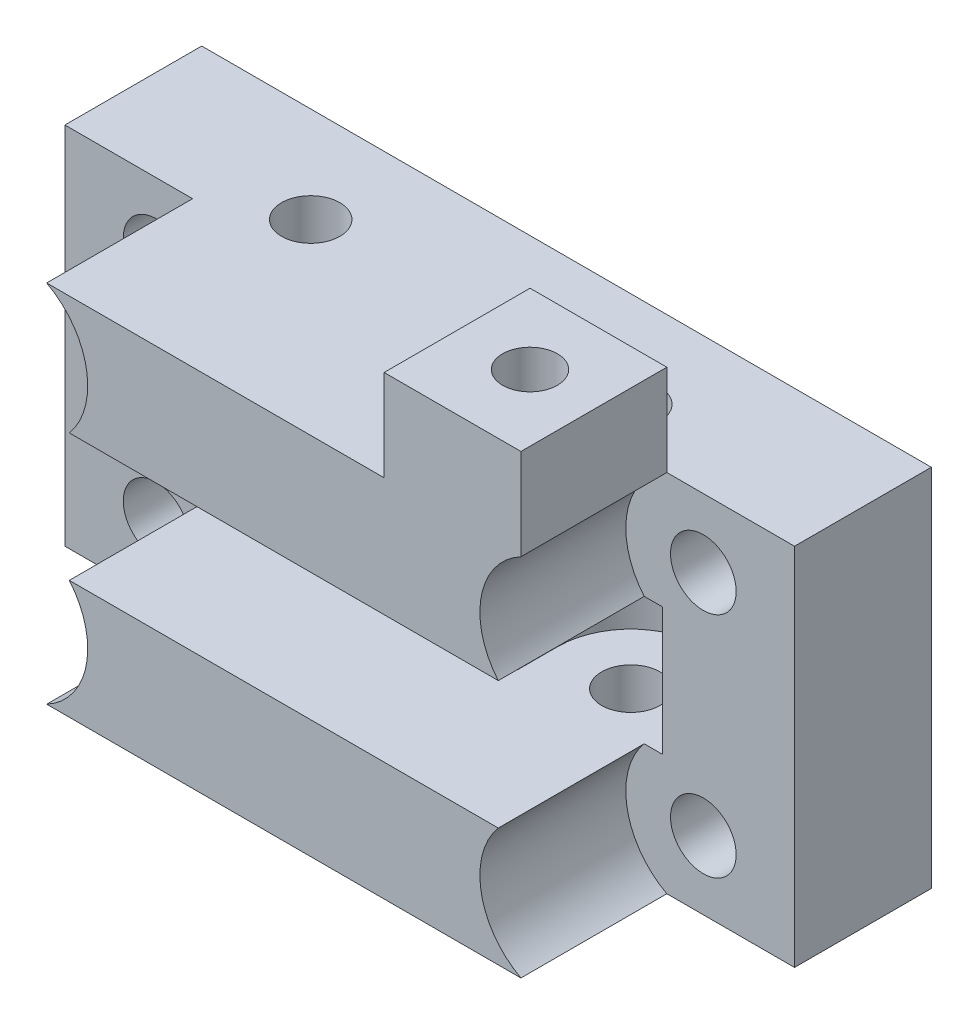
SolidWorks part; units mm, degrees
ref_plane "Front Plane" through (0, 0, 0) normal (0, 0, 1) x (1, 0, 0)
ref_plane "Top Plane" through (0, 0, 0) normal (0, 1, 0) x (1, 0, 0)
ref_plane "Right Plane" through (0, 0, 0) normal (1, 0, 0) x (0, 0, -1)
sketch "Sketch1" plane through (0, 0, 0) normal (0, 0, 1) x (1, 0, 0)
  line L0 (-25.4, 12.7) -> (25.4, -12.7) construction
  line L1 (-25.4, -12.7) -> (25.4, -12.7)
  line L2 (-25.4, -12.7) -> (-25.4, 12.7)
  line L3 (-25.4, 12.7) -> (25.4, 12.7)
  line L4 (25.4, -12.7) -> (25.4, 12.7)
  point P6 (0, 0)
  dimension "D1" = 50.8
  dimension "D2" = 25.4
extrude "Boss-Extrude1" add sketch "Sketch1" along normal mid plane 9.525
sketch "Sketch2" plane through (0, 0, 4.7625) normal (0, 0, 1) x (1, 0, 0)
  line L0 (-25.4, -12.7) -> (25.4, -12.7) construction
  line L1 (-25.4, 12.7) -> (-25.4, -12.7) construction
  circle A0 centre (-19.05, 7.9375) radius 2.286
  dimension "D1" = 4.572
  dimension "D2" = 20.6375
  dimension "D3" = 6.35
extrude "Cut-Extrude1" cut sketch "Sketch2" against normal through all
sketch "Sketch4" plane through (0, 0, 0) normal (0, 1, 0) x (1, 0, 0)
  line L7 (25.4, -4.7625) -> (-25.4, -4.7625) construction
  line L8 (-16.2242, -1.905) -> (-16.2243, -4.7625)
  line L9 (-6.0642, -1.905) -> (-6.0643, -4.7625)
  line L10 (-6.0643, -4.7625) -> (-16.2243, -4.7625)
  line L11 (-25.4, -4.7625) -> (-25.4, 4.7625) construction
  arc A2 (-6.0642, -1.905) -> (-16.2242, -1.905) centre (-11.1442, -1.905) ccw
  dimension "D1" = 10.16
  dimension "D2" = 2.8575
  dimension "D3" = 14.2558
extrude "Cut-Extrude2" cut sketch "Sketch4" against normal mid plane 8.89
sketch "Sketch5" plane through (0, 12.7, 0) normal (0, 1, 0) x (1, 0, 0)
  line L0 (25.4, -4.7625) -> (-25.4, -4.7625) construction
  line L1 (-25.4, -4.7625) -> (-25.4, 4.7625) construction
  circle A0 centre (-11.1442, -1.905) radius 2.032
  dimension "D3" = 4.064
  dimension "D1" = 2.8575
  dimension "D2" = 14.2558
extrude "Cut-Extrude3" cut sketch "Sketch5" against normal through all
sketch "Sketch6" plane through (0, 0, 4.7625) normal (0, 0, 1) x (1, 0, 0)
  line L0 (-16.51, 12.7) -> (16.51, 12.7)
  line L1 (25.4, 12.7) -> (-25.4, 12.7) construction
  line L2 (-14.9347, 4.445) -> (14.9347, 4.445)
  line L3 (-16.2242, 4.445) -> (-6.0642, 4.445) construction
  arc A0 (-14.9347, 4.445) -> (-16.51, 12.7) centre (-19.05, 7.9375) ccw
  arc A1 (16.51, 12.7) -> (14.9347, 4.445) centre (19.05, 7.9375) ccw
  dimension "D1" = 10.795
  dimension "D2" = 38.1
  dimension "D3" = 29.8695
extrude "Boss-Extrude2" add sketch "Sketch6" along normal blind 10.16
mirror "Mirror1" about plane through (0, 0, 0) normal (0, 1, 0) of "Boss-Extrude2", "Cut-Extrude1"
mirror "Mirror2" about plane through (0, 0, 0) normal (1, 0, 0) of "Cut-Extrude3", "Mirror1", "Cut-Extrude2"
sketch "Sketch7" plane through (0, 12.7, 0) normal (0, 1, 0) x (1, 0, 0)
  line L0 (16.51, -14.9225) -> (-16.51, -14.9225) construction
  line L1 (16.51, -4.7625) -> (6.985, -4.7625)
  line L2 (16.51, -4.7625) -> (16.51, -14.9225)
  line L3 (16.51, -14.9225) -> (6.985, -14.9225)
  line L4 (6.985, -4.7625) -> (6.985, -14.9225)
  dimension "D1" = 9.525
extrude "Boss-Extrude3" add sketch "Sketch7" along normal blind 6.35
sketch "Sketch8" plane through (0, 19.05, 0) normal (0, 1, 0) x (1, 0, 0)
  line L0 (11.8867, -9.6673) -> (6.985, -9.8425) construction
  line L1 (6.985, -4.7625) -> (6.985, -14.9225) construction
  line L2 (11.8867, -9.6673) -> (11.8867, -4.7625) construction
  line L3 (16.51, -4.7625) -> (6.985, -4.7625) construction
  circle A0 centre (11.8867, -9.6673) radius 1.905
  dimension "D1" = 3.81
extrude "Cut-Extrude4" cut sketch "Sketch8" against normal blind 6.35 contours A0
